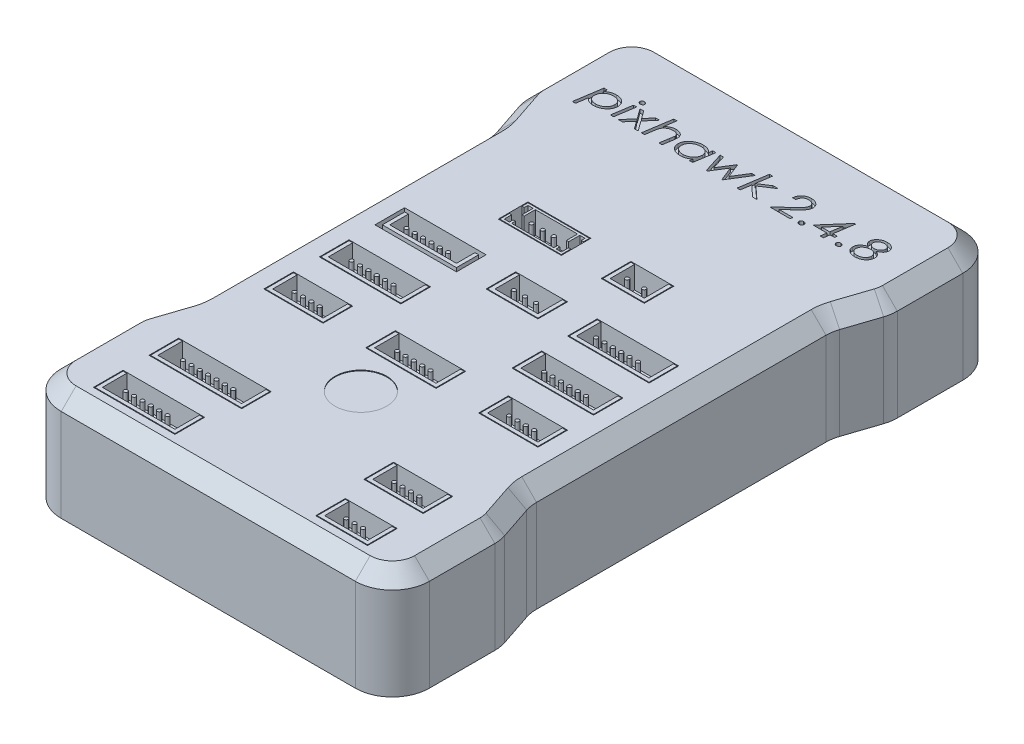
SolidWorks part; units mm, degrees
ref_plane "Front Plane" through (0, 0, 0) normal (0, 0, 1) x (1, 0, 0)
ref_plane "Top Plane" through (0, 0, 0) normal (0, 1, 0) x (1, 0, 0)
ref_plane "Right Plane" through (0, 0, 0) normal (1, 0, 0) x (0, 0, -1)
sketch "Sketch1" plane through (0, 0, 0) normal (0, 1, 0) x (1, 0, 0)
  line L6 (-19.85, 41) -> (19.85, 41)
  line L7 (24.85, 36) -> (24.85, 27.1614)
  line L8 (24.5934, 25.5802) -> (23.1066, 21.1198)
  line L9 (22.85, 19.5386) -> (22.85, -19.5386)
  line L12 (-22.85, 19.5386) -> (-22.85, -19.5386)
  line L13 (-24.5934, 25.5802) -> (-23.1066, 21.1198)
  line L14 (-24.85, 36) -> (-24.85, 27.1614)
  line L15 (-24.85, -36) -> (-24.85, -27.1614)
  line L16 (-24.5934, -25.5802) -> (-23.1066, -21.1198)
  line L17 (24.5934, -25.5802) -> (23.1066, -21.1198)
  line L18 (24.85, -36) -> (24.85, -27.1614)
  line L19 (-19.85, -41) -> (19.85, -41)
  arc A0 (19.85, 41) -> (24.85, 36) centre (19.85, 36) cw
  arc A1 (23.1066, 21.1198) -> (22.85, 19.5386) centre (27.85, 19.5386) ccw
  arc A2 (24.85, 27.1614) -> (24.5934, 25.5802) centre (19.85, 27.1614) cw
  arc A3 (-23.1066, 21.1198) -> (-22.85, 19.5386) centre (-27.85, 19.5386) cw
  arc A4 (-24.85, 27.1614) -> (-24.5934, 25.5802) centre (-19.85, 27.1614) ccw
  arc A5 (-19.85, 41) -> (-24.85, 36) centre (-19.85, 36) ccw
  arc A6 (-19.85, -41) -> (-24.85, -36) centre (-19.85, -36) cw
  arc A7 (-24.85, -27.1614) -> (-24.5934, -25.5802) centre (-19.85, -27.1614) cw
  arc A8 (-23.1066, -21.1198) -> (-22.85, -19.5386) centre (-27.85, -19.5386) ccw
  arc A9 (24.85, -27.1614) -> (24.5934, -25.5802) centre (19.85, -27.1614) ccw
  arc A10 (23.1066, -21.1198) -> (22.85, -19.5386) centre (27.85, -19.5386) cw
  arc A11 (19.85, -41) -> (24.85, -36) centre (19.85, -36) ccw
  point P8 (24.85, 41)
  point P12 (22.85, 20.35)
  point P15 (24.85, 26.35)
  point P44 (24.85, -26.35)
  point P45 (22.85, -20.35)
  point P46 (24.85, -41)
  point P48 (0, 0)
  dimension "D6" = 5
  dimension "D7" = 5
  dimension "D1" = 49.7
  dimension "D2" = 39.0772
  dimension "D3" = 82
  dimension "D4" = 2
  dimension "D5" = 6
  dimension "D8" = 41
extrude "Boss-Extrude1" add sketch "Sketch1" along normal blind 16
chamfer "Chamfer2" distance 2 angle 45 24 edges at (22.9146, 16, 20.3395) (22.85, 16, 0) (23.85, 16, 23.35) (22.9146, 16, -20.3395) (24.7854, 16, 26.3605) (23.85, 16, -23.35) (24.85, 16, 31.5807) (24.7854, 16, -26.3605) (23.3855, 16, 39.5355) (24.85, 16, -31.5807) (0, 16, 41) (23.3855, 16, -39.5355) (-23.3855, 16, 39.5355) (0, 16, -41) (-24.85, 16, 31.5807) (-23.3855, 16, -39.5355) (-24.7854, 16, 26.3605) (-24.85, 16, -31.5807) (-23.85, 16, 23.35) (-24.7854, 16, -26.3605) (-22.9146, 16, 20.3395) (-23.85, 16, -23.35) (-22.85, 16, 0) (-22.9146, 16, -20.3395)
chamfer "Chamfer3" distance 3.5 distance2 1.5 24 edges at (-22.85, 0, 0) (-22.9146, 0, 20.3395) (-22.9146, 0, -20.3395) (-23.85, 0, 23.35) (-23.85, 0, -23.35) (-24.7854, 0, 26.3605) (-24.7854, 0, -26.3605) (-24.85, 0, 31.5807) (-24.85, 0, -31.5807) (-23.3855, 0, 39.5355) (-23.3855, 0, -39.5355) (0, 0, 41) (0, 0, -41) (23.3855, 0, 39.5355) (23.3855, 0, -39.5355) (24.85, 0, 31.5807) (24.85, 0, -31.5807) (24.7854, 0, 26.3605) (24.7854, 0, -26.3605) (23.85, 0, 23.35) (23.85, 0, -23.35) (22.9146, 0, 20.3395) (22.9146, 0, -20.3395) (22.85, 0, 0) first distance on face at (0, 0, 0)
sketch "Sketch4" plane through (0, 0, 0) normal (0, -1, 0) x (1, 0, 0)
  line L0 (0, 0) -> (0, 37.5) construction
  line L1 (-18.35, 36.5) -> (-12.35, 36.5)
  line L2 (-20.35, 34.5) -> (-20.35, 28.5)
  line L3 (-18.35, 26.5) -> (-12.35, 26.5)
  line L4 (-10.35, 34.5) -> (-10.35, 28.5)
  line L5 (19.85, 37.5) -> (-19.85, 37.5) construction
  line L6 (0, 0) -> (-19.35, 0) construction
  line L7 (-19.35, 19.5386) -> (-19.35, -19.5386) construction
  line L8 (-21.35, 36) -> (-21.35, 27.1614) construction
  line L9 (18.35, 26.5) -> (12.35, 26.5)
  line L10 (10.35, 34.5) -> (10.35, 28.5)
  line L11 (18.35, 36.5) -> (12.35, 36.5)
  line L12 (20.35, 34.5) -> (20.35, 28.5)
  line L13 (20.35, -34.5) -> (20.35, -28.5)
  line L14 (18.35, -36.5) -> (12.35, -36.5)
  line L15 (10.35, -34.5) -> (10.35, -28.5)
  line L16 (18.35, -26.5) -> (12.35, -26.5)
  line L17 (-18.35, -26.5) -> (-12.35, -26.5)
  line L18 (-10.35, -34.5) -> (-10.35, -28.5)
  line L19 (-18.35, -36.5) -> (-12.35, -36.5)
  line L20 (-20.35, -34.5) -> (-20.35, -28.5)
  line L22 (-10.75, 17.75) -> (10.75, 17.75)
  line L23 (-12.75, 15.75) -> (-12.75, -15.75)
  line L24 (-10.75, -17.75) -> (10.75, -17.75)
  line L25 (12.75, 15.75) -> (12.75, -15.75)
  arc A0 (-12.35, 26.5) -> (-10.35, 28.5) centre (-12.35, 28.5) ccw
  arc A1 (-20.35, 28.5) -> (-18.35, 26.5) centre (-18.35, 28.5) ccw
  arc A2 (-18.35, 36.5) -> (-20.35, 34.5) centre (-18.35, 34.5) ccw
  arc A3 (-12.35, 36.5) -> (-10.35, 34.5) centre (-12.35, 34.5) cw
  arc A4 (12.35, 26.5) -> (10.35, 28.5) centre (12.35, 28.5) cw
  arc A5 (12.35, 36.5) -> (10.35, 34.5) centre (12.35, 34.5) ccw
  arc A6 (20.35, 28.5) -> (18.35, 26.5) centre (18.35, 28.5) cw
  arc A7 (18.35, 36.5) -> (20.35, 34.5) centre (18.35, 34.5) cw
  arc A8 (20.35, -28.5) -> (18.35, -26.5) centre (18.35, -28.5) ccw
  arc A9 (18.35, -36.5) -> (20.35, -34.5) centre (18.35, -34.5) ccw
  arc A10 (12.35, -36.5) -> (10.35, -34.5) centre (12.35, -34.5) cw
  arc A11 (12.35, -26.5) -> (10.35, -28.5) centre (12.35, -28.5) ccw
  arc A12 (-12.35, -26.5) -> (-10.35, -28.5) centre (-12.35, -28.5) cw
  arc A13 (-12.35, -36.5) -> (-10.35, -34.5) centre (-12.35, -34.5) ccw
  arc A14 (-20.35, -28.5) -> (-18.35, -26.5) centre (-18.35, -28.5) cw
  arc A15 (-18.35, -36.5) -> (-20.35, -34.5) centre (-18.35, -34.5) cw
  arc A16 (-12.75, -15.75) -> (-10.75, -17.75) centre (-10.75, -15.75) ccw
  arc A17 (10.75, -17.75) -> (12.75, -15.75) centre (10.75, -15.75) ccw
  arc A18 (10.75, 17.75) -> (12.75, 15.75) centre (10.75, 15.75) cw
  arc A19 (-10.75, 17.75) -> (-12.75, 15.75) centre (-10.75, 15.75) ccw
  point P16 (-10.35, 26.5)
  point P19 (-20.35, 26.5)
  point P24 (-10.35, 36.5)
  point P65 (0, -17.75)
  point P66 (-12.75, 0)
  point P69 (-12.75, -17.75)
  point P72 (12.75, -17.75)
  point P75 (12.75, 17.75)
  dimension "D5" = 2
  dimension "D8" = 2
  dimension "D1" = 10
  dimension "D2" = 10
  dimension "D3" = 1
  dimension "D4" = 1
  dimension "D6" = 35.5
  dimension "D7" = 25.5
extrude "Cut-Extrude2" cut sketch "Sketch4" against normal blind 0.5
sketch "Sketch5" plane through (0, 16, 0) normal (0, 1, 0) x (1, 0, 0)
  line L0 (-20.85, 19.5386) -> (-20.85, -19.5386) construction
  line L1 (-10.85, 13) -> (-2.35, 13)
  line L2 (-10.85, 13) -> (-10.85, 9)
  line L3 (-10.85, 9) -> (-2.35, 9)
  line L4 (-2.35, 13) -> (-2.35, 9)
  line L5 (3.05, 13) -> (8.85, 13)
  line L6 (3.05, 13) -> (3.05, 9)
  line L7 (3.05, 9) -> (8.85, 9)
  line L8 (8.85, 13) -> (8.85, 9)
  line L9 (20.85, -19.5386) -> (20.85, 19.5386) construction
  line L10 (19.85, 39) -> (-19.85, 39) construction
  line L11 (-18.5, -3.5) -> (-7.5, -3.5)
  line L12 (-18.5, 4) -> (-7.5, 4)
  line L13 (-18.5, 4) -> (-18.5, 0)
  line L14 (-18.5, 0) -> (-7.5, 0)
  line L15 (-7.5, 4) -> (-7.5, 0)
  line L16 (-3.5, 4) -> (3.5, 4)
  line L17 (-3.5, 4) -> (-3.5, 0)
  line L18 (-3.5, 0) -> (3.5, 0)
  line L19 (3.5, 4) -> (3.5, 0)
  line L20 (7.5, 4) -> (18.5, 4)
  line L21 (7.5, 4) -> (7.5, 0)
  line L22 (7.5, 0) -> (18.5, 0)
  line L23 (18.5, 4) -> (18.5, 0)
  line L24 (-18.5, -3.5) -> (-18.5, -7.5)
  line L25 (-18.5, -7.5) -> (-7.5, -7.5)
  line L26 (-7.5, -3.5) -> (-7.5, -7.5)
  line L27 (7.5, -3.5) -> (18.5, -3.5)
  line L28 (7.5, -3.5) -> (7.5, -7.5)
  line L29 (7.5, -7.5) -> (18.5, -7.5)
  line L30 (18.5, -3.5) -> (18.5, -7.5)
  line L31 (-19.85, -39) -> (19.85, -39) construction
  line L32 (-18.5, -11) -> (-10.5, -11)
  line L33 (-18.5, -11) -> (-18.5, -15)
  line L34 (-18.5, -15) -> (-10.5, -15)
  line L35 (-10.5, -11) -> (-10.5, -15)
  line L36 (-4.75, -11) -> (4.75, -11)
  line L37 (-4.75, -11) -> (-4.75, -15)
  line L38 (-4.75, -15) -> (4.75, -15)
  line L39 (4.75, -11) -> (4.75, -15)
  line L40 (10.5, -11) -> (18.5, -11)
  line L41 (10.5, -11) -> (10.5, -15)
  line L42 (10.5, -15) -> (18.5, -15)
  line L43 (18.5, -11) -> (18.5, -15)
  line L44 (-18.5, -34) -> (-7.5, -34)
  line L45 (-18.5, -34) -> (-18.5, -38)
  line L46 (-18.5, -38) -> (-7.5, -38)
  line L47 (-7.5, -34) -> (-7.5, -38)
  line L49 (-18.5, -26.5) -> (-6, -26.5)
  line L50 (-18.5, -26.5) -> (-18.5, -30.5)
  line L51 (-18.5, -30.5) -> (-6, -30.5)
  line L52 (-6, -26.5) -> (-6, -30.5)
  line L53 (18.5, -26.5) -> (10.5, -26.5)
  line L54 (18.5, -26.5) -> (18.5, -30.5)
  line L55 (18.5, -30.5) -> (10.5, -30.5)
  line L56 (10.5, -26.5) -> (10.5, -30.5)
  line L57 (18.5, -34) -> (11.5, -34)
  line L58 (18.5, -34) -> (18.5, -38)
  line L59 (18.5, -38) -> (11.5, -38)
  line L60 (11.5, -34) -> (11.5, -38)
  point P12 (3.05, 11)
  point P13 (-2.35, 11)
  point P49 (0, 4)
  point P51 (0, -11)
  dimension "D1" = 8.5
  dimension "D2" = 4
  dimension "D3" = 4
  dimension "D4" = 5.8
  dimension "D5" = 10
  dimension "D6" = 12
  dimension "D7" = 26
  dimension "D8" = 11
  dimension "D9" = 4
  dimension "D10" = 4
  dimension "D11" = 4
  dimension "D12" = 7
  dimension "D13" = 4
  dimension "D14" = 4
  dimension "D15" = 11
  dimension "D16" = 5
  dimension "D17" = 8
  dimension "D18" = 11
  dimension "D19" = 4
  dimension "D20" = 4
  dimension "D21" = 11
  dimension "D22" = 3.5
  dimension "D23" = 3.5
  dimension "D24" = 8
  dimension "D25" = 4
  dimension "D26" = 3.5
  dimension "D27" = 9.5
  dimension "D28" = 4
  dimension "D29" = 4
  dimension "D30" = 11
  dimension "D31" = 4
  dimension "D32" = 1
  dimension "D33" = 12.5
  dimension "D34" = 4
  dimension "D35" = 3.5
  dimension "D36" = 8
  dimension "D37" = 4
  dimension "D38" = 7
  dimension "D39" = 4
  dimension "D40" = 1
  dimension "D41" = 3.5
extrude "Cut-Extrude3" cut sketch "Sketch5" against normal blind 4
sketch "Sketch6" plane through (0, 12, 0) normal (0, 1, 0) x (1, 0, 0)
  line L0 (-10.85, 11) -> (-3.85, 11) construction
  line L1 (-10.85, 13) -> (-10.85, 9) construction
  line L2 (-2.35, 9) -> (-2.35, 13) construction
  line L25 (-9.85, 11) -> (-9.35, 11)
  line L27 (-6.6, 11) -> (-6.6, 9.5) construction
  line L46 (-9.45, 12.6) -> (-3.75, 12.6)
  line L47 (-3.75, 11.1) -> (-3.75, 12.6)
  line L48 (-3.45, 11.1) -> (-3.75, 11.1)
  line L49 (-3.45, 12.6) -> (-3.45, 11.1)
  line L50 (-2.75, 12.6) -> (-3.45, 12.6)
  line L51 (-2.75, 12.1) -> (-2.75, 12.6)
  line L52 (-2.45, 12.1) -> (-2.75, 12.1)
  line L53 (-2.45, 12.9) -> (-2.45, 12.1)
  line L54 (-10.75, 12.9) -> (-2.45, 12.9)
  line L55 (-10.75, 12.1) -> (-10.75, 12.9)
  line L56 (-10.75, 12.1) -> (-10.45, 12.1)
  line L57 (-10.45, 12.1) -> (-10.45, 12.6)
  line L58 (-10.45, 12.6) -> (-9.75, 12.6)
  line L59 (-9.75, 12.6) -> (-9.75, 11.1)
  line L60 (-9.75, 11.1) -> (-9.45, 11.1)
  line L61 (-9.45, 11.1) -> (-9.45, 12.6)
  line L62 (-2.75, 9.4) -> (-2.75, 10.4)
  line L63 (-2.75, 10.4) -> (-2.45, 10.4)
  line L64 (-2.45, 10.4) -> (-2.45, 9.1)
  line L65 (-10.75, 9.1) -> (-2.45, 9.1)
  line L66 (-10.75, 10.4) -> (-10.75, 9.1)
  line L67 (-10.45, 10.4) -> (-10.75, 10.4)
  line L68 (-10.45, 9.4) -> (-10.45, 10.4)
  line L69 (-9.75, 9.4) -> (-10.45, 9.4)
  line L70 (-9.75, 9.9) -> (-9.75, 9.4)
  line L71 (-9.45, 9.9) -> (-9.75, 9.9)
  line L72 (-9.45, 9.4) -> (-9.45, 9.9)
  line L73 (-3.75, 9.4) -> (-9.45, 9.4)
  line L74 (-3.75, 9.4) -> (-3.75, 9.9)
  line L75 (-3.75, 9.9) -> (-3.45, 9.9)
  line L76 (-3.45, 9.9) -> (-3.45, 9.4)
  line L77 (-3.45, 9.4) -> (-2.75, 9.4)
  line L78 (-10.85, 12) -> (-10.85, 13) construction
  line L79 (-10.85, 13) -> (-2.35, 13) construction
  line L80 (-10.85, 12) -> (-10.35, 12) construction
  line L81 (-10.35, 12) -> (-10.35, 12.5) construction
  line L82 (-10.35, 12.5) -> (-9.85, 12.5) construction
  line L83 (-9.85, 12.5) -> (-9.85, 11) construction
  line L84 (-2.35, 13) -> (-2.35, 12) construction
  line L85 (-2.35, 12) -> (-2.85, 12) construction
  line L86 (-2.85, 12) -> (-2.85, 12.5) construction
  line L87 (-2.85, 12.5) -> (-3.35, 12.5) construction
  line L88 (-3.35, 12.5) -> (-3.35, 11) construction
  line L89 (-3.35, 11) -> (-2.35, 11) construction
  line L90 (-3.35, 11) -> (-3.85, 11) construction
  line L91 (-3.85, 11) -> (-3.85, 12.5) construction
  line L92 (-9.35, 12.5) -> (-3.85, 12.5) construction
  line L93 (-9.35, 11) -> (-9.35, 12.5) construction
  dimension "D2" = 0.5
  dimension "D8" = 0.1
extrude "Boss-Extrude2" add sketch "Sketch6" along normal up to surface (4 mm away) contours L60 L61 L46 L47 L48 L49 L50 L51 L52 L53 L54 L55 L56 L57 L58 L59 | L77 L76 L75 L74 L73 L72 L71 L70 L69 L68 L67 L66 L65 L64 L63 L62 region at (-9.5349, 12, -11.85) region at (-2.666, 12, -9.9) up to face at (13, 16, -2)
sketch "Sketch7" plane through (0, 12, 0) normal (0, 1, 0) x (1, 0, 0)
  line L0 (-10.75, 9.1) -> (-2.45, 9.1) construction
  line L1 (-10.75, 12.9) -> (-2.45, 12.9) construction
  line L2 (-10.75, 9.1) -> (-2.45, 9.1)
  line L3 (-10.75, 12.9) -> (-2.45, 12.9)
  line L4 (-10.75, 12.9) -> (-10.75, 9.1)
  line L5 (-2.45, 12.9) -> (-2.45, 9.1)
extrude "Boss-Extrude3" add sketch "Sketch7" along normal blind 1
sketch "Sketch8" plane through (0, 13, 0) normal (0, 1, 0) x (1, 0, 0)
  line L6 (-10.75, 11) -> (-2.45, 11) construction
  circle A0 centre (-6.6, 10.75) radius 0.25
  circle A1 centre (-5.1, 10.75) radius 0.25
  circle A2 centre (-8.1, 10.75) radius 0.25
  point P9 (-6.6, 11)
  dimension "D1" = 0.5
  dimension "D2" = 0.25
  dimension "D3" = 1.5
  dimension "D4" = 1.5
extrude "Boss-Extrude4" add sketch "Sketch8" along normal up to surface (3 mm away) up to face at (13, 16, -2)
sketch "Sketch9" plane through (0, 12, 0) normal (0, 1, 0) x (1, 0, 0)
  line L0 (8.75, 12.9) -> (8.25, 12.9)
  line L1 (3.15, 12.9) -> (3.15, 9.1)
  line L2 (3.15, 9.1) -> (8.75, 9.1)
  line L3 (8.75, 9.1) -> (8.75, 12.9)
  line L4 (3.65, 12.9) -> (3.65, 9.6)
  line L5 (3.65, 9.6) -> (8.25, 9.6)
  line L6 (8.25, 9.6) -> (8.25, 12.9)
  line L7 (3.65, 12.9) -> (3.15, 12.9)
  line L8 (3.05, 13) -> (3.05, 9) construction
  line L9 (3.05, 9) -> (8.85, 9) construction
  line L10 (8.85, 9) -> (8.85, 13) construction
  line L11 (8.85, 13) -> (3.05, 13) construction
  dimension "D1" = 0.5
  dimension "D2" = 0.1
  dimension "D3" = 0.1
  dimension "D4" = 0.5
  dimension "D5" = 0.1
  dimension "D6" = 0.5
  dimension "D7" = 0.1
extrude "Boss-Extrude5" add sketch "Sketch9" along normal up to surface (4 mm away) up to face at (13, 16, -2)
sketch "Sketch10" plane through (0, 12, 0) normal (0, 1, 0) x (1, 0, 0)
  line L0 (8.75, 12.9) -> (8.75, 9.1) construction
  line L1 (3.15, 9.1) -> (8.75, 9.1) construction
  line L2 (3.15, 9.1) -> (3.15, 12.9) construction
  line L3 (3.15, 12.9) -> (3.65, 12.9) construction
  line L4 (8.75, 12.9) -> (8.75, 9.1)
  line L5 (3.15, 9.1) -> (8.75, 9.1)
  line L6 (3.15, 9.1) -> (3.15, 12.9)
  line L7 (3.15, 12.9) -> (3.65, 12.9)
  line L8 (3.65, 12.9) -> (8.75, 12.9)
extrude "Boss-Extrude6" add sketch "Sketch10" along normal blind 1
sketch "Sketch11" plane through (0, 13, 0) normal (0, 1, 0) x (1, 0, 0)
  line L0 (3.15, 11) -> (8.75, 11) construction
  line L1 (3.15, 12.9) -> (3.15, 9.1) construction
  line L2 (8.75, 9.1) -> (8.75, 12.9) construction
  circle A0 centre (4.8, 10.75) radius 0.25
  circle A1 centre (7.1, 10.75) radius 0.25
  point P10 (5.95, 11)
  dimension "D1" = 0.5
  dimension "D2" = 1.15
  dimension "D3" = 1.15
extrude "Boss-Extrude7" add sketch "Sketch11" along normal up to surface (3 mm away) up to face at (13, 16, -2)
sketch "Sketch12" plane through (0, 12, 0) normal (0, 1, 0) x (1, 0, 0)
  line L0 (-8, 3.5) -> (-18, 3.5)
  line L1 (-18, 3.5) -> (-18, 0.5)
  line L2 (-18, 0.5) -> (-8, 0.5)
  line L3 (-8, 0.5) -> (-8, 3.5)
extrude "Boss-Extrude8" add sketch "Sketch12" along normal blind 1
sketch "Sketch13" plane through (0, 13, 0) normal (0, 1, 0) x (1, 0, 0)
  line L0 (-18, 3.5) -> (-18, 0.5)
  line L1 (-18, 0.5) -> (-8, 0.5)
  line L2 (-8, 0.5) -> (-8, 3.5)
  line L3 (-8, 3.5) -> (-8.5, 3.5)
  line L4 (-8, 3.5) -> (-18, 3.5) construction
  line L5 (-8.5, 3.5) -> (-8.5, 1)
  line L6 (-8.5, 1) -> (-17.5, 1)
  line L7 (-17.5, 1) -> (-17.5, 3.5)
  line L8 (-17.5, 3.5) -> (-18, 3.5)
  dimension "D1" = 0.5
  dimension "D2" = 0.5
  dimension "D3" = 0.5
extrude "Boss-Extrude9" add sketch "Sketch13" along normal up to surface (3 mm away) up to face at (13, 16, -2)
sketch "Sketch14" plane through (0, 13, 0) normal (0, 1, 0) x (1, 0, 0)
  line L0 (-17.5, 2) -> (-8.5, 2) construction
  line L1 (-17.5, 1) -> (-17.5, 3.5) construction
  line L3 (-17.5, 3.5) -> (-17.5, 1) construction
  line L4 (-8.5, 1) -> (-8.5, 3.5) construction
  circle A0 centre (-16, 1.75) radius 0.25
  circle A1 centre (-14.875, 1.75) radius 0.25
  circle A2 centre (-13.75, 1.75) radius 0.25
  circle A3 centre (-12.625, 1.75) radius 0.25
  circle A5 centre (-11.5, 1.75) radius 0.25
  circle A6 centre (-10.375, 1.75) radius 0.25
  dimension "D1" = 0.5
  dimension "D2" = 1.5
  dimension "D3" = 1.125
  dimension "D4" = 1.125
  dimension "D5" = 1.125
  dimension "D6" = 1.125
  dimension "D7" = 1.125
extrude "Boss-Extrude10" add sketch "Sketch14" along normal up to surface (3 mm away) up to face at (13, 16, -2)
sketch "Sketch15" plane through (0, 12, 0) normal (0, 1, 0) x (1, 0, 0)
  line L0 (3.4, 3.9) -> (-3.4, 3.9)
  line L1 (-3.4, 3.9) -> (-3.4, 0.1)
  line L2 (-3.4, 0.1) -> (3.4, 0.1)
  line L3 (3.4, 0.1) -> (3.4, 3.9)
extrude "Boss-Extrude11" add sketch "Sketch15" along normal blind 1
sketch "Sketch16" plane through (0, 13, 0) normal (0, 1, 0) x (1, 0, 0)
  line L0 (-3.4, 0.1) -> (-3.4, 3.9)
  line L1 (-3.4, 3.9) -> (-2.9, 3.9)
  line L2 (3.4, 3.9) -> (-3.4, 3.9) construction
  line L3 (-2.9, 3.9) -> (-2.9, 0.6)
  line L4 (-2.9, 0.6) -> (2.9, 0.6)
  line L5 (2.9, 0.6) -> (2.9, 3.9)
  line L6 (2.9, 3.9) -> (3.4, 3.9)
  line L7 (3.4, 0.1) -> (3.4, 3.9) construction
  line L8 (3.4, 3.9) -> (3.4, 0.1)
  line L9 (3.4, 0.1) -> (-3.4, 0.1)
  point P15 (3.4, 2)
  dimension "D1" = 0.5
  dimension "D2" = 0.5
  dimension "D3" = 0.5
extrude "Boss-Extrude12" add sketch "Sketch16" along normal up to surface (3 mm away) up to face at (13, 16, -2)
sketch "Sketch17" plane through (0, 13, 0) normal (0, 1, 0) x (1, 0, 0)
  line L0 (-2.9, 2) -> (2.9, 2) construction
  line L1 (-2.9, 3.9) -> (-2.9, 0.6) construction
  line L2 (2.9, 3.9) -> (2.9, 0.6) construction
  circle A0 centre (0, 1.75) radius 0.25
  circle A1 centre (-1.5, 1.75) radius 0.25
  circle A2 centre (1.5, 1.75) radius 0.25
  point P14 (0, 1.5109)
  dimension "D1" = 0.5
  dimension "D2" = 0.5
  dimension "D3" = 1.5
  dimension "D4" = 1.5
extrude "Boss-Extrude13" add sketch "Sketch17" along normal up to surface (3 mm away) up to face at (13, 16, -2)
sketch "Sketch18" plane through (0, 12, 0) normal (0, 1, 0) x (1, 0, 0)
  line L0 (18.4, 3.9) -> (7.6, 3.9)
  line L1 (7.6, 3.9) -> (7.6, 0.1)
  line L2 (7.6, 0.1) -> (18.4, 0.1)
  line L3 (18.4, 0.1) -> (18.4, 3.9)
extrude "Boss-Extrude14" add sketch "Sketch18" along normal blind 1
sketch "Sketch19" plane through (0, 13, 0) normal (0, 1, 0) x (1, 0, 0)
  line L0 (7.6, 0.1) -> (7.6, 3.9)
  line L1 (7.6, 3.9) -> (8.1, 3.9)
  line L2 (18.4, 3.9) -> (7.6, 3.9) construction
  line L3 (8.1, 3.9) -> (8.1, 0.6)
  line L4 (8.1, 0.6) -> (17.9, 0.6)
  line L5 (17.9, 0.6) -> (17.9, 3.9)
  line L6 (17.9, 3.9) -> (18.4, 3.9)
  line L7 (18.4, 3.9) -> (7.6, 3.9) construction
  line L8 (18.4, 3.9) -> (18.4, 0.1)
  line L9 (18.4, 0.1) -> (7.6, 0.1)
  dimension "D1" = 0.5
  dimension "D2" = 0.5
  dimension "D3" = 0.5
extrude "Boss-Extrude15" add sketch "Sketch19" along normal up to surface (3 mm away) up to face at (13, 16, -2)
sketch "Sketch20" plane through (0, 13, 0) normal (0, 1, 0) x (1, 0, 0)
  line L0 (8.1, 1.997) -> (17.9, 1.997) construction
  line L1 (8.1, 3.9) -> (8.1, 0.6) construction
  line L2 (17.9, 3.9) -> (17.9, 0.6) construction
  line L3 (8.1, 0.6) -> (8.1, 3.9) construction
  circle A0 centre (14.1223, 1.747) radius 0.25
  circle A1 centre (15.2523, 1.747) radius 0.25
  circle A2 centre (11.8623, 1.75) radius 0.247
  circle A3 centre (10.7323, 1.747) radius 0.25
  circle A4 centre (12.9923, 1.75) radius 0.247
  circle A5 centre (9.6, 1.747) radius 0.25
  dimension "D1" = 0.5
  dimension "D2" = 0.5
  dimension "D3" = 1.1323
  dimension "D4" = 1.13
  dimension "D5" = 1.13
  dimension "D6" = 1.13
  dimension "D7" = 1.13
  dimension "D8" = 1.5
extrude "Boss-Extrude16" add sketch "Sketch20" along normal up to surface (3 mm away) up to face at (13, 16, -2)
sketch "Sketch22" plane through (0, 12, 0) normal (0, 1, 0) x (1, 0, 0)
  line L0 (-7.6, -3.6) -> (-18.4, -3.6)
  line L1 (-18.4, -3.6) -> (-18.4, -7.4)
  line L2 (-18.4, -7.4) -> (-7.6, -7.4)
  line L3 (-7.6, -7.4) -> (-7.6, -3.6)
extrude "Boss-Extrude17" add sketch "Sketch22" along normal blind 1
sketch "Sketch23" plane through (0, 13, 0) normal (0, 1, 0) x (1, 0, 0)
  line L0 (-18.4, -7.4) -> (-18.4, -3.6)
  line L1 (-18.4, -3.6) -> (-18.4, -7.4) construction
  line L2 (-18.4, -3.6) -> (-18.4, -7.4) construction
  line L3 (-18.4, -3.6) -> (-17.9, -3.6)
  line L4 (-7.6, -3.6) -> (-18.4, -3.6) construction
  line L5 (-17.9, -3.6) -> (-17.9, -6.9)
  line L6 (-17.9, -6.9) -> (-8.1, -6.9)
  line L7 (-8.1, -6.9) -> (-8.1, -3.6)
  line L8 (-8.1, -3.6) -> (-7.6, -3.6)
  line L9 (-7.6, -3.6) -> (-18.4, -3.6) construction
  line L10 (-7.6, -3.6) -> (-7.6, -7.4)
  line L11 (-7.6, -7.4) -> (-18.4, -7.4)
  dimension "D1" = 0.5
  dimension "D2" = 0.5
  dimension "D3" = 0.5
extrude "Boss-Extrude18" add sketch "Sketch23" along normal up to surface (3 mm away) up to face at (13, 16, -2)
sketch "Sketch24" plane through (0, 13, 0) normal (0, 1, 0) x (1, 0, 0)
  line L0 (-17.9, -5.5) -> (-8.1, -5.5) construction
  line L1 (-17.9, -3.6) -> (-17.9, -6.9) construction
  line L2 (-8.1, -3.6) -> (-8.1, -6.9) construction
  line L3 (-17.9, -6.9) -> (-17.9, -3.6) construction
  circle A0 centre (-15.9, -5.75) radius 0.25
  circle A1 centre (-14.77, -5.75) radius 0.25
  circle A2 centre (-13.64, -5.75) radius 0.25
  circle A3 centre (-12.51, -5.75) radius 0.25
  circle A4 centre (-11.38, -5.75) radius 0.25
  circle A5 centre (-10.25, -5.75) radius 0.25
  dimension "D1" = 0.5
  dimension "D2" = 2
  dimension "D3" = 6
extrude "Boss-Extrude19" add sketch "Sketch24" along normal up to surface (3 mm away) up to face at (13, 16, -2)
sketch "Sketch25" plane through (0, 12, 0) normal (0, 1, 0) x (1, 0, 0)
  line L0 (18.4, -3.6) -> (7.6, -3.6)
  line L1 (7.6, -3.6) -> (7.6, -7.4)
  line L2 (7.6, -7.4) -> (18.4, -7.4)
  line L3 (18.4, -7.4) -> (18.4, -3.6)
extrude "Boss-Extrude20" add sketch "Sketch25" along normal blind 1
sketch "Sketch26" plane through (0, 13, 0) normal (0, 1, 0) x (1, 0, 0)
  line L0 (7.6, -3.6) -> (7.6, -7.4)
  line L1 (7.6, -7.4) -> (18.4, -7.4)
  line L2 (18.4, -7.4) -> (18.4, -3.6)
  line L3 (18.4, -3.6) -> (17.9, -3.6)
  line L4 (18.4, -3.6) -> (7.6, -3.6) construction
  line L5 (17.9, -3.6) -> (17.9, -6.9)
  line L6 (17.9, -6.9) -> (8.1, -6.9)
  line L7 (8.1, -6.9) -> (8.1, -3.6)
  line L8 (8.1, -3.6) -> (7.6, -3.6)
  dimension "D1" = 0.5
  dimension "D2" = 0.5
  dimension "D3" = 0.5
extrude "Boss-Extrude21" add sketch "Sketch26" along normal up to surface (3 mm away) up to face at (13, 16, -2)
sketch "Sketch27" plane through (0, 13, 0) normal (0, 1, 0) x (1, 0, 0)
  line L0 (8.1, -5.5) -> (17.9, -5.5) construction
  line L1 (8.1, -3.6) -> (8.1, -6.9) construction
  line L2 (17.9, -3.6) -> (17.9, -6.9) construction
  circle A0 centre (10.1, -5.75) radius 0.25
  circle A1 centre (11.23, -5.75) radius 0.25
  circle A2 centre (12.36, -5.75) radius 0.25
  circle A3 centre (13.49, -5.75) radius 0.25
  circle A4 centre (14.62, -5.75) radius 0.25
  circle A5 centre (15.75, -5.75) radius 0.25
  dimension "D1" = 0.5
  dimension "D2" = 2
  dimension "D3" = 6
extrude "Boss-Extrude22" add sketch "Sketch27" along normal up to surface (3 mm away) up to face at (13, 16, -2)
sketch "Sketch28" plane through (0, 12, 0) normal (0, 1, 0) x (1, 0, 0)
  line L0 (-10.6, -11.1) -> (-18.4, -11.1)
  line L1 (-18.4, -11.1) -> (-18.4, -14.9)
  line L2 (-18.4, -14.9) -> (-10.6, -14.9)
  line L3 (-10.6, -14.9) -> (-10.6, -11.1)
extrude "Boss-Extrude23" add sketch "Sketch28" along normal blind 1
sketch "Sketch29" plane through (0, 13, 0) normal (0, 1, 0) x (1, 0, 0)
  line L0 (-18.4, -11.1) -> (-18.4, -14.9)
  line L1 (-18.4, -14.9) -> (-10.6, -14.9)
  line L2 (-10.6, -14.9) -> (-10.6, -11.1)
  line L3 (-10.6, -11.1) -> (-11.1, -11.1)
  line L4 (-10.6, -11.1) -> (-18.4, -11.1) construction
  line L5 (-11.1, -11.1) -> (-11.1, -14.4)
  line L6 (-11.1, -14.4) -> (-17.9, -14.4)
  line L7 (-17.9, -14.4) -> (-17.9, -11.1)
  line L8 (-17.9, -11.1) -> (-18.4, -11.1)
  dimension "D1" = 0.5
  dimension "D2" = 0.5
  dimension "D3" = 0.5
extrude "Boss-Extrude24" add sketch "Sketch29" along normal up to surface (3 mm away) up to face at (13, 16, -2)
sketch "Sketch30" plane through (0, 13, 0) normal (0, 1, 0) x (1, 0, 0)
  line L0 (-17.9, -13) -> (-11.1, -13) construction
  line L1 (-17.9, -11.1) -> (-17.9, -14.4) construction
  line L2 (-11.1, -11.1) -> (-11.1, -14.4) construction
  line L3 (-17.9, -14.4) -> (-17.9, -11.1) construction
  circle A0 centre (-16.1, -13.25) radius 0.25
  circle A1 centre (-14.97, -13.25) radius 0.25
  circle A2 centre (-13.84, -13.25) radius 0.25
  circle A3 centre (-12.71, -13.25) radius 0.25
  dimension "D1" = 0.5
  dimension "D2" = 4
  dimension "D3" = 1.8
extrude "Boss-Extrude25" add sketch "Sketch30" along normal up to surface (3 mm away) up to face at (13, 16, -2)
sketch "Sketch31" plane through (0, 12, 0) normal (0, 1, 0) x (1, 0, 0)
  line L0 (4.65, -11.1) -> (-4.65, -11.1)
  line L1 (-4.65, -11.1) -> (-4.65, -14.9)
  line L2 (-4.65, -14.9) -> (4.65, -14.9)
  line L3 (4.65, -14.9) -> (4.65, -11.1)
extrude "Boss-Extrude26" add sketch "Sketch31" along normal blind 1
sketch "Sketch32" plane through (0, 13, 0) normal (0, 1, 0) x (1, 0, 0)
  line L0 (-4.65, -14.9) -> (-4.65, -11.1)
  line L1 (-4.65, -11.1) -> (-4.15, -11.1)
  line L2 (4.65, -11.1) -> (-4.65, -11.1) construction
  line L3 (-4.15, -11.1) -> (-4.15, -14.4)
  line L4 (-4.15, -14.4) -> (4.15, -14.4)
  line L5 (4.15, -14.4) -> (4.15, -11.1)
  line L6 (4.65, -11.1) -> (-4.65, -11.1) construction
  line L7 (4.15, -11.1) -> (4.65, -11.1)
  line L8 (4.65, -11.1) -> (4.65, -14.9)
  line L9 (4.65, -14.9) -> (-4.65, -14.9)
  dimension "D1" = 0.5
  dimension "D2" = 0.5
  dimension "D3" = 0.5
extrude "Boss-Extrude27" add sketch "Sketch32" along normal up to surface (3 mm away) up to face at (13, 16, -2)
sketch "Sketch33" plane through (0, 13, 0) normal (0, 1, 0) x (1, 0, 0)
  line L0 (-4.15, -13) -> (4.15, -13) construction
  line L1 (-4.15, -14.4) -> (-4.15, -11.1) construction
  line L2 (4.15, -14.4) -> (4.15, -11.1) construction
  circle A0 centre (0, -13.25) radius 0.25
  circle A1 centre (1.13, -13.2565) radius 0.25
  circle A2 centre (-1.13, -13.25) radius 0.25
  circle A5 centre (2.26, -13.263) radius 0.25
  circle A7 centre (-2.26, -13.237) radius 0.25
  point P15 (0, -13.4891)
  dimension "D1" = 0.5
  dimension "D2" = 1.13
  dimension "D3" = 1.13
  dimension "D4" = 1.13
  dimension "D5" = 1.13
extrude "Boss-Extrude28" add sketch "Sketch33" along normal up to surface (3 mm away) up to face at (13, 16, -2)
sketch "Sketch34" plane through (0, 12, 0) normal (0, 1, 0) x (1, 0, 0)
  line L0 (18.4, -11.1) -> (10.6, -11.1)
  line L1 (10.6, -11.1) -> (10.6, -14.9)
  line L2 (10.6, -14.9) -> (18.4, -14.9)
  line L3 (18.4, -14.9) -> (18.4, -11.1)
extrude "Boss-Extrude29" add sketch "Sketch34" along normal blind 1
sketch "Sketch35" plane through (0, 13, 0) normal (0, 1, 0) x (1, 0, 0)
  line L0 (10.6, -11.1) -> (10.6, -14.9)
  line L1 (10.6, -14.9) -> (18.4, -14.9)
  line L2 (18.4, -14.9) -> (18.4, -11.1)
  line L3 (18.4, -11.1) -> (17.9, -11.1)
  line L4 (18.4, -11.1) -> (10.6, -11.1) construction
  line L5 (17.9, -11.1) -> (17.9, -14.4)
  line L6 (17.9, -14.4) -> (11.1, -14.4)
  line L7 (11.1, -14.4) -> (11.1, -11.1)
  line L8 (18.4, -11.1) -> (10.6, -11.1) construction
  line L9 (11.1, -11.1) -> (10.6, -11.1)
  dimension "D1" = 0.5
  dimension "D2" = 0.5
  dimension "D3" = 0.5
extrude "Boss-Extrude30" add sketch "Sketch35" along normal up to surface (3 mm away) up to face at (13, 16, -2)
sketch "Sketch36" plane through (0, 13, 0) normal (0, 1, 0) x (1, 0, 0)
  line L0 (11.1, -13) -> (17.9, -13) construction
  line L1 (11.1, -11.1) -> (11.1, -14.4) construction
  line L2 (17.9, -11.1) -> (17.9, -14.4) construction
  line L3 (11.1, -14.4) -> (11.1, -11.1) construction
  circle A0 centre (12.85, -13.25) radius 0.25
  circle A1 centre (13.98, -13.25) radius 0.25
  circle A2 centre (15.11, -13.25) radius 0.25
  circle A3 centre (16.24, -13.25) radius 0.25
  dimension "D1" = 0.5
  dimension "D3" = 1.75
  dimension "D2" = 4
extrude "Boss-Extrude31" add sketch "Sketch36" along normal up to surface (3 mm away) up to face at (13, 16, -2)
sketch "Sketch37" plane through (0, 12, 0) normal (0, 1, 0) x (1, 0, 0)
  line L0 (-6.1, -26.6) -> (-18.4, -26.6)
  line L1 (-18.4, -26.6) -> (-18.4, -30.4)
  line L2 (-18.4, -30.4) -> (-6.1, -30.4)
  line L3 (-6.1, -30.4) -> (-6.1, -26.6)
extrude "Boss-Extrude32" add sketch "Sketch37" along normal blind 1
sketch "Sketch38" plane through (0, 13, 0) normal (0, 1, 0) x (1, 0, 0)
  line L0 (-18.4, -26.6) -> (-18.4, -30.4)
  line L1 (-18.4, -30.4) -> (-6.1, -30.4)
  line L2 (-6.1, -30.4) -> (-6.1, -26.6)
  line L3 (-6.1, -26.6) -> (-6.6, -26.6)
  line L4 (-6.1, -26.6) -> (-18.4, -26.6) construction
  line L5 (-6.6, -26.6) -> (-6.6, -29.9)
  line L6 (-6.6, -29.9) -> (-17.9, -29.9)
  line L7 (-17.9, -29.9) -> (-17.9, -26.6)
  line L8 (-6.1, -26.6) -> (-18.4, -26.6) construction
  line L9 (-17.9, -26.6) -> (-18.4, -26.6)
  dimension "D1" = 0.5
  dimension "D2" = 0.5
  dimension "D3" = 0.5
extrude "Boss-Extrude33" add sketch "Sketch38" along normal up to surface (3 mm away) up to face at (13, 16, -2)
sketch "Sketch39" plane through (0, 13, 0) normal (0, 1, 0) x (1, 0, 0)
  line L0 (-17.9, -28.5238) -> (-6.6, -28.5238) construction
  line L1 (-17.9, -29.9) -> (-17.9, -26.6) construction
  line L2 (-6.6, -29.9) -> (-6.6, -26.6) construction
  circle A0 centre (-12.25, -28.7738) radius 0.25
  circle A1 centre (-11.12, -28.7738) radius 0.25
  circle A2 centre (-14.51, -28.7738) radius 0.25
  circle A3 centre (-13.38, -28.7738) radius 0.25
  circle A4 centre (-9.99, -28.7738) radius 0.25
  circle A5 centre (-8.86, -28.7738) radius 0.25
  circle A6 centre (-15.64, -28.7738) radius 0.25
  point P21 (-12.25, -29.0129)
  point P23 (-12.25, -28.5238)
  dimension "D1" = 0.5
  dimension "D2" = 1.13
  dimension "D3" = 1.13
  dimension "D4" = 1.13
  dimension "D5" = 1.13
  dimension "D6" = 1.13
  dimension "D7" = 1.13
extrude "Boss-Extrude34" add sketch "Sketch39" along normal up to surface (3 mm away) up to face at (13, 16, -2)
sketch "Sketch40" plane through (0, 12, 0) normal (0, 1, 0) x (1, 0, 0)
  line L0 (18.4, -26.6) -> (10.6, -26.6)
  line L1 (10.6, -26.6) -> (10.6, -30.4)
  line L2 (10.6, -30.4) -> (18.4, -30.4)
  line L3 (18.4, -30.4) -> (18.4, -26.6)
extrude "Boss-Extrude35" add sketch "Sketch40" along normal blind 1
sketch "Sketch41" plane through (0, 13, 0) normal (0, 1, 0) x (1, 0, 0)
  line L0 (10.6, -30.4) -> (10.6, -26.6)
  line L1 (10.6, -26.6) -> (11.1, -26.6)
  line L2 (18.4, -26.6) -> (10.6, -26.6) construction
  line L3 (11.1, -26.6) -> (11.1, -29.9)
  line L4 (11.1, -29.9) -> (17.9, -29.9)
  line L5 (17.9, -29.9) -> (17.9, -26.6)
  line L6 (18.4, -26.6) -> (10.6, -26.6) construction
  line L7 (17.9, -26.6) -> (18.4, -26.6)
  line L8 (18.4, -26.6) -> (18.4, -30.4)
  line L9 (18.4, -30.4) -> (10.6, -30.4)
  dimension "D1" = 0.5
  dimension "D2" = 0.5
  dimension "D3" = 0.5
extrude "Boss-Extrude36" add sketch "Sketch41" along normal up to surface (3 mm away) up to face at (13, 16, -2)
sketch "Sketch42" plane through (0, 13, 0) normal (0, 1, 0) x (1, 0, 0)
  line L0 (11.1, -28.5) -> (17.9, -28.5) construction
  line L1 (11.1, -26.6) -> (11.1, -29.9) construction
  line L2 (17.9, -26.6) -> (17.9, -29.9) construction
  line L3 (11.1, -29.9) -> (11.1, -26.6) construction
  circle A0 centre (12.85, -28.75) radius 0.25
  circle A1 centre (13.98, -28.75) radius 0.25
  circle A2 centre (15.11, -28.75) radius 0.25
  circle A3 centre (16.24, -28.75) radius 0.25
  dimension "D1" = 0.5
  dimension "D3" = 1.75
  dimension "D2" = 4
extrude "Boss-Extrude37" add sketch "Sketch42" along normal up to surface (3 mm away) up to face at (13, 16, -2)
sketch "Sketch43" plane through (0, 12, 0) normal (0, 1, 0) x (1, 0, 0)
  line L0 (-7.6, -34.1) -> (-18.4, -34.1)
  line L1 (-18.4, -34.1) -> (-18.4, -37.9)
  line L2 (-18.4, -37.9) -> (-7.6, -37.9)
  line L3 (-7.6, -37.9) -> (-7.6, -34.1)
extrude "Boss-Extrude38" add sketch "Sketch43" along normal blind 1
sketch "Sketch44" plane through (0, 13, 0) normal (0, 1, 0) x (1, 0, 0)
  line L0 (-18.4, -34.1) -> (-18.4, -37.9)
  line L1 (-18.4, -37.9) -> (-7.6, -37.9) construction
  line L2 (-18.4, -37.9) -> (-7.6, -37.9) construction
  line L3 (-18.4, -37.9) -> (-7.6, -37.9)
  line L4 (-7.6, -37.9) -> (-7.6, -34.1)
  line L5 (-7.6, -34.1) -> (-8.1, -34.1)
  line L6 (-7.6, -34.1) -> (-18.4, -34.1) construction
  line L7 (-8.1, -34.1) -> (-8.1, -37.4)
  line L8 (-8.1, -37.4) -> (-17.9, -37.4)
  line L9 (-17.9, -37.4) -> (-17.9, -34.1)
  line L10 (-17.9, -34.1) -> (-18.4, -34.1)
  dimension "D1" = 0.5
  dimension "D2" = 0.5
  dimension "D3" = 0.5
extrude "Boss-Extrude39" add sketch "Sketch44" along normal up to surface (3 mm away) up to face at (13, 16, -2)
sketch "Sketch45" plane through (0, 13, 0) normal (0, 1, 0) x (1, 0, 0)
  line L0 (-17.9, -36) -> (-8.1, -36) construction
  line L1 (-17.9, -37.4) -> (-17.9, -34.1) construction
  line L2 (-8.1, -34.1) -> (-8.1, -37.4) construction
  line L3 (-17.9, -34.1) -> (-17.9, -37.4) construction
  circle A0 centre (-15.9, -36.25) radius 0.25
  circle A1 centre (-14.77, -36.25) radius 0.25
  circle A2 centre (-13.64, -36.25) radius 0.25
  circle A3 centre (-12.51, -36.25) radius 0.25
  circle A4 centre (-11.38, -36.25) radius 0.25
  circle A5 centre (-10.25, -36.25) radius 0.25
  dimension "D1" = 0.5
  dimension "D3" = 2
  dimension "D2" = 6
extrude "Boss-Extrude40" add sketch "Sketch45" along normal up to surface (3 mm away) up to face at (13, 16, -2)
sketch "Sketch46" plane through (0, 12, 0) normal (0, 1, 0) x (1, 0, 0)
  line L0 (18.4, -34.1) -> (11.6, -34.1)
  line L1 (11.6, -34.1) -> (11.6, -37.9)
  line L2 (11.6, -37.9) -> (18.4, -37.9)
  line L3 (18.4, -37.9) -> (18.4, -34.1)
extrude "Boss-Extrude41" add sketch "Sketch46" along normal blind 1
sketch "Sketch47" plane through (0, 13, 0) normal (0, 1, 0) x (1, 0, 0)
  line L0 (11.6, -34.1) -> (11.6, -37.9)
  line L1 (11.6, -37.9) -> (18.4, -37.9)
  line L2 (18.4, -37.9) -> (18.4, -34.1)
  line L3 (18.4, -34.1) -> (17.9, -34.1)
  line L4 (18.4, -34.1) -> (11.6, -34.1) construction
  line L5 (17.9, -34.1) -> (17.9, -37.4)
  line L6 (17.9, -37.4) -> (12.1, -37.4)
  line L7 (12.1, -37.4) -> (12.1, -34.1)
  line L8 (12.1, -34.1) -> (11.6, -34.1)
  dimension "D1" = 0.5
  dimension "D2" = 0.5
  dimension "D3" = 0.5
extrude "Boss-Extrude42" add sketch "Sketch47" along normal up to surface (3 mm away) up to face at (13, 16, -2)
sketch "Sketch48" plane through (0, 13, 0) normal (0, 1, 0) x (1, 0, 0)
  line L0 (12.1, -36) -> (17.9, -36) construction
  line L1 (12.1, -34.1) -> (12.1, -37.4) construction
  line L2 (17.9, -34.1) -> (17.9, -37.4) construction
  circle A0 centre (13.87, -36.25) radius 0.25
  circle A1 centre (15, -36.25) radius 0.25
  circle A2 centre (16.13, -36.25) radius 0.25
  point P9 (15, -36)
  dimension "D1" = 0.5
  dimension "D2" = 3
extrude "Boss-Extrude43" add sketch "Sketch48" along normal up to surface (3 mm away) up to face at (13, 16, -2)
sketch "Sketch49" plane through (0, 16, 0) normal (0, 1, 0) x (1, 0, 0)
  line L0 (4.65, -14.9) -> (-4.65, -14.9) construction
  circle A0 centre (0, -20.4) radius 3.5
  dimension "D1" = 7
  dimension "D2" = 5.5
extrude "Cut-Extrude4" cut sketch "Sketch49" against normal blind 0.1
sketch "Sketch51" plane through (0, 0, -41) normal (0, 0, -1) x (-1, 0, 0)
  line L0 (-19.85, 10.5) -> (19.85, 10.5)
  line L4 (-19.85, 14) -> (-19.85, 1.5)
  line L5 (-19.85, 1.5) -> (19.85, 1.5)
  line L6 (19.85, 1.5) -> (19.85, 14)
  line L7 (19.85, 14) -> (-19.85, 14)
  line L8 (-19.85, 10.5) -> (-19.85, 1.5)
  line L9 (-19.85, 1.5) -> (19.85, 1.5)
  line L10 (19.85, 1.5) -> (19.85, 10.5)
  dimension "D2" = 9
  dimension "D1" = 0
extrude "Cut-Extrude5" cut sketch "Sketch51" against normal blind 7
sketch "Sketch52" plane through (0, 0, -34) normal (0, 0, -1) x (-1, 0, 0)
  line L0 (-17.37, 9.2594) -> (-17.37, 2.7406)
  line L1 (-14.8887, 9.2594) -> (-14.8887, 2.7406)
  line L2 (-18.6094, 9.2594) -> (-18.6094, 2.7406) construction
  line L3 (-17.3687, 9.2594) -> (-17.3687, 2.7406)
  line L4 (-19.85, 9.2594) -> (-19.85, 2.7406)
  line L5 (-19.85, 10.5) -> (-19.85, 1.5) construction
  line L6 (-19.85, 1.5) -> (19.85, 1.5) construction
  line L7 (-16.1294, 9.2594) -> (-16.1294, 2.7406) construction
  line L8 (-14.89, 9.2594) -> (-14.89, 2.7406)
  line L9 (-12.4087, 9.2594) -> (-12.4087, 2.7406)
  line L10 (-13.6494, 9.2594) -> (-13.6494, 2.7406) construction
  line L11 (-12.41, 9.2594) -> (-12.41, 2.7406)
  line L12 (-9.9287, 9.2594) -> (-9.9287, 2.7406)
  line L13 (-11.1694, 9.2594) -> (-11.1694, 2.7406) construction
  line L14 (-9.93, 9.2594) -> (-9.93, 2.7406)
  line L15 (-7.4487, 9.2594) -> (-7.4487, 2.7406)
  line L16 (-8.6894, 9.2594) -> (-8.6894, 2.7406) construction
  line L17 (-7.45, 9.2594) -> (-7.45, 2.7406)
  line L18 (-4.9687, 9.2594) -> (-4.9687, 2.7406)
  line L19 (-6.2094, 9.2594) -> (-6.2094, 2.7406) construction
  line L20 (-4.97, 9.2594) -> (-4.97, 2.7406)
  line L21 (-2.4887, 9.2594) -> (-2.4887, 2.7406)
  line L22 (-3.7294, 9.2594) -> (-3.7294, 2.7406) construction
  line L23 (-2.49, 9.2594) -> (-2.49, 2.7406)
  line L24 (-0.0087, 9.2594) -> (-0.0087, 2.7406)
  line L25 (-1.2494, 9.2594) -> (-1.2494, 2.7406) construction
  line L26 (-0.01, 9.2594) -> (-0.01, 2.7406)
  line L27 (2.4713, 9.2594) -> (2.4713, 2.7406)
  line L28 (1.2306, 9.2594) -> (1.2306, 2.7406) construction
  line L29 (2.47, 9.2594) -> (2.47, 2.7406)
  line L30 (4.9513, 9.2594) -> (4.9513, 2.7406)
  line L31 (3.7106, 9.2594) -> (3.7106, 2.7406) construction
  line L32 (4.95, 9.2594) -> (4.95, 2.7406)
  line L33 (7.4313, 9.2594) -> (7.4313, 2.7406)
  line L34 (6.1906, 9.2594) -> (6.1906, 2.7406) construction
  line L35 (7.43, 9.2594) -> (7.43, 2.7406)
  line L36 (9.9113, 9.2594) -> (9.9113, 2.7406)
  line L37 (8.6706, 9.2594) -> (8.6706, 2.7406) construction
  line L38 (9.91, 9.2594) -> (9.91, 2.7406)
  line L39 (12.3913, 9.2594) -> (12.3913, 2.7406)
  line L40 (11.1506, 9.2594) -> (11.1506, 2.7406) construction
  line L41 (12.39, 9.2594) -> (12.39, 2.7406)
  line L42 (14.8713, 9.2594) -> (14.8713, 2.7406)
  line L43 (13.6306, 9.2594) -> (13.6306, 2.7406) construction
  line L44 (14.87, 9.2594) -> (14.87, 2.7406)
  line L45 (17.3513, 9.2594) -> (17.3513, 2.7406)
  line L46 (16.1106, 9.2594) -> (16.1106, 2.7406) construction
  line L47 (17.35, 9.2594) -> (17.35, 2.7406)
  line L48 (19.8313, 9.2594) -> (19.8313, 2.7406)
  line L49 (18.5906, 9.2594) -> (18.5906, 2.7406) construction
  arc A0 (-17.3687, 9.2594) -> (-19.85, 9.2594) centre (-18.6094, 9.2594) ccw
  arc A1 (-19.85, 2.7406) -> (-17.3687, 2.7406) centre (-18.6094, 2.7406) ccw
  arc A2 (-14.8887, 9.2594) -> (-17.37, 9.2594) centre (-16.1294, 9.2594) ccw
  arc A3 (-17.37, 2.7406) -> (-14.8887, 2.7406) centre (-16.1294, 2.7406) ccw
  arc A4 (-12.4087, 9.2594) -> (-14.89, 9.2594) centre (-13.6494, 9.2594) ccw
  arc A5 (-14.89, 2.7406) -> (-12.4087, 2.7406) centre (-13.6494, 2.7406) ccw
  arc A6 (-9.9287, 9.2594) -> (-12.41, 9.2594) centre (-11.1694, 9.2594) ccw
  arc A7 (-12.41, 2.7406) -> (-9.9287, 2.7406) centre (-11.1694, 2.7406) ccw
  arc A8 (-7.4487, 9.2594) -> (-9.93, 9.2594) centre (-8.6894, 9.2594) ccw
  arc A9 (-9.93, 2.7406) -> (-7.4487, 2.7406) centre (-8.6894, 2.7406) ccw
  arc A10 (-4.9687, 9.2594) -> (-7.45, 9.2594) centre (-6.2094, 9.2594) ccw
  arc A11 (-7.45, 2.7406) -> (-4.9687, 2.7406) centre (-6.2094, 2.7406) ccw
  arc A12 (-2.4887, 9.2594) -> (-4.97, 9.2594) centre (-3.7294, 9.2594) ccw
  arc A13 (-4.97, 2.7406) -> (-2.4887, 2.7406) centre (-3.7294, 2.7406) ccw
  arc A14 (-0.0087, 9.2594) -> (-2.49, 9.2594) centre (-1.2494, 9.2594) ccw
  arc A15 (-2.49, 2.7406) -> (-0.0087, 2.7406) centre (-1.2494, 2.7406) ccw
  arc A16 (2.4713, 9.2594) -> (-0.01, 9.2594) centre (1.2306, 9.2594) ccw
  arc A17 (-0.01, 2.7406) -> (2.4713, 2.7406) centre (1.2306, 2.7406) ccw
  arc A18 (4.9513, 9.2594) -> (2.47, 9.2594) centre (3.7106, 9.2594) ccw
  arc A19 (2.47, 2.7406) -> (4.9513, 2.7406) centre (3.7106, 2.7406) ccw
  arc A20 (7.4313, 9.2594) -> (4.95, 9.2594) centre (6.1906, 9.2594) ccw
  arc A21 (4.95, 2.7406) -> (7.4313, 2.7406) centre (6.1906, 2.7406) ccw
  arc A22 (9.9113, 9.2594) -> (7.43, 9.2594) centre (8.6706, 9.2594) ccw
  arc A23 (7.43, 2.7406) -> (9.9113, 2.7406) centre (8.6706, 2.7406) ccw
  arc A24 (12.3913, 9.2594) -> (9.91, 9.2594) centre (11.1506, 9.2594) ccw
  arc A25 (9.91, 2.7406) -> (12.3913, 2.7406) centre (11.1506, 2.7406) ccw
  arc A26 (14.8713, 9.2594) -> (12.39, 9.2594) centre (13.6306, 9.2594) ccw
  arc A27 (12.39, 2.7406) -> (14.8713, 2.7406) centre (13.6306, 2.7406) ccw
  arc A28 (17.3513, 9.2594) -> (14.87, 9.2594) centre (16.1106, 9.2594) ccw
  arc A29 (14.87, 2.7406) -> (17.3513, 2.7406) centre (16.1106, 2.7406) ccw
  arc A30 (19.8313, 9.2594) -> (17.35, 9.2594) centre (18.5906, 9.2594) ccw
  arc A31 (17.35, 2.7406) -> (19.8313, 2.7406) centre (18.5906, 2.7406) ccw
  circle A32 centre (-18.6094, 6) radius 0.25
  circle A33 centre (-18.6094, 9.2594) radius 0.25
  circle A34 centre (-18.6094, 2.7406) radius 0.25
  circle A35 centre (-16.1294, 9.2594) radius 0.25
  circle A36 centre (-16.1294, 6) radius 0.25
  circle A37 centre (-16.1294, 2.7406) radius 0.25
  circle A38 centre (-13.6494, 9.2594) radius 0.25
  circle A39 centre (-13.6494, 6) radius 0.25
  circle A40 centre (-13.6494, 2.7406) radius 0.25
  circle A41 centre (-11.1694, 9.2594) radius 0.25
  circle A42 centre (-11.1694, 6) radius 0.25
  circle A43 centre (-11.1694, 2.7406) radius 0.25
  circle A44 centre (-8.6894, 9.2594) radius 0.25
  circle A45 centre (-8.6894, 6) radius 0.25
  circle A46 centre (-8.6894, 2.7406) radius 0.25
  circle A47 centre (-6.2094, 9.2594) radius 0.25
  circle A48 centre (-6.2094, 6) radius 0.25
  circle A49 centre (-6.2094, 2.7406) radius 0.25
  circle A50 centre (-3.7294, 9.2594) radius 0.25
  circle A51 centre (-3.7294, 6) radius 0.25
  circle A52 centre (-3.7294, 2.7406) radius 0.25
  circle A53 centre (-1.2494, 9.2594) radius 0.25
  circle A54 centre (-1.2494, 6) radius 0.25
  circle A55 centre (-1.2494, 2.7406) radius 0.25
  circle A56 centre (1.2306, 9.2594) radius 0.25
  circle A57 centre (1.2306, 6) radius 0.25
  circle A58 centre (1.2306, 2.7406) radius 0.25
  circle A59 centre (3.7106, 9.2594) radius 0.25
  circle A60 centre (3.7106, 6) radius 0.25
  circle A61 centre (3.7106, 2.7406) radius 0.25
  circle A62 centre (6.1906, 9.2594) radius 0.25
  circle A63 centre (6.1906, 6) radius 0.25
  circle A64 centre (6.1906, 2.7406) radius 0.25
  circle A65 centre (8.6706, 9.2594) radius 0.25
  circle A66 centre (8.6706, 6) radius 0.25
  circle A67 centre (8.6706, 2.7406) radius 0.25
  circle A68 centre (11.1506, 9.2594) radius 0.25
  circle A69 centre (11.1506, 6) radius 0.25
  circle A70 centre (11.1506, 2.7406) radius 0.25
  circle A71 centre (13.6306, 9.2594) radius 0.25
  circle A72 centre (13.6306, 6) radius 0.25
  circle A73 centre (13.6306, 2.7406) radius 0.25
  circle A74 centre (16.1106, 9.2594) radius 0.25
  circle A75 centre (16.1106, 6) radius 0.25
  circle A76 centre (16.1106, 2.7406) radius 0.25
  circle A77 centre (18.5906, 9.2594) radius 0.25
  circle A78 centre (18.5906, 6) radius 0.25
  circle A79 centre (18.5906, 2.7406) radius 0.25
  point P0 (-18.6094, 6)
  point P9 (-18.6094, 10.5)
  point P10 (-18.6094, 1.5)
  point P15 (-16.1294, 6)
  point P22 (-13.6494, 6)
  point P29 (-11.1694, 6)
  point P36 (-8.6894, 6)
  point P43 (-6.2094, 6)
  point P50 (-3.7294, 6)
  point P57 (-1.2494, 6)
  point P64 (1.2306, 6)
  point P71 (3.7106, 6)
  point P78 (6.1906, 6)
  point P85 (8.6706, 6)
  point P92 (11.1506, 6)
  point P99 (13.6306, 6)
  point P106 (16.1106, 6)
  point P113 (18.5906, 6)
  dimension "D5" = 0.5
  dimension "D6" = 0.5
  dimension "D7" = 0.5
  dimension "D1" = 2.4813
  dimension "D2" = 0
  dimension "D3" = 9
  dimension "D4" = 16
  dimension "D8" = 16
extrude "Boss-Extrude46" add sketch "Sketch52" along normal up to surface (7 mm away) contours A33 | A32 | A34 | A35 | A36 | A37 | A40 | A39 | A38 | A41 | A42 | A46 | A49 | A48 | A47 | A50 | A51 | A52 | A55 | A54 | A53 | A56 | A57 | A58 | A59 | A61 | A64 | A63 | A62 | A65 | A66 | A67 | A70 | A69 | A68 | A71 | A72 | A73 | A76 | A75 | A74 | A77 | A78 | A79 | A43 | A45 | A44 | A60 region at (18.6094, 6, -34) region at (18.6094, 9.2594, -34) region at (18.6094, 2.7406, -34) region at (16.1294, 9.2594, -34) region at (16.1294, 6, -34) region at (16.1294, 2.7406, -34) region at (13.6494, 9.2594, -34) region at (13.6494, 6, -34) region at (13.6494, 2.7406, -34) region at (11.1694, 9.2594, -34) region at (11.1694, 6, -34) region at (11.1694, 2.7406, -34) region at (8.6894, 9.2594, -34) region at (8.6894, 6, -34) region at (8.6894, 2.7406, -34) region at (6.2094, 9.2594, -34) region at (6.2094, 6, -34) region at (6.2094, 2.7406, -34) region at (3.7294, 9.2594, -34) region at (3.7294, 6, -34) region at (3.7294, 2.7406, -34) region at (1.2494, 9.2594, -34) region at (1.2494, 6, -34) region at (1.2494, 2.7406, -34) region at (-1.2306, 9.2594, -34) region at (-1.2306, 6, -34) region at (-1.2306, 2.7406, -34) region at (-3.7106, 9.2594, -34) region at (-3.7106, 2.7406, -34) region at (-6.1906, 9.2594, -34) region at (-6.1906, 6, -34) region at (-6.1906, 2.7406, -34) region at (-8.6706, 9.2594, -34) region at (-8.6706, 6, -34) region at (-8.6706, 2.7406, -34) region at (-11.1506, 9.2594, -34) region at (-11.1506, 6, -34) region at (-11.1506, 2.7406, -34) region at (-13.6306, 9.2594, -34) region at (-13.6306, 6, -34) region at (-13.6306, 2.7406, -34) region at (-16.1106, 9.2594, -34) region at (-16.1106, 6, -34) region at (-16.1106, 2.7406, -34) region at (-18.5906, 9.2594, -34) region at (-18.5906, 6, -34) region at (-18.5906, 2.7406, -34) up to face at (0, 12.25, -41)
sketch "Sketch53" plane through (0, 16, 0) normal (0, 1, 0) x (1, 0, 0)
  line L0 (-22.85, 28.7392) -> (22.85, 28.7392) construction
  line L1 (-22.85, 36) -> (-22.85, 27.1614) construction
  line L2 (22.85, 27.1614) -> (22.85, 36) construction
  text T0 "<i>pixhawk 2.4.8</i>" font "Century Gothic" height in points 14
extrude "Cut-Extrude6" cut sketch "Sketch53" against normal blind 0.5
sketch "Sketch54" plane through (0, 0.5, 0) normal (0, -1, 0) x (1, 0, 0)
  circle A0 centre (0, 0) radius 2.5
  dimension "D1" = 5
extrude "Boss-Extrude47" add sketch "Sketch54" along normal blind 0.1
